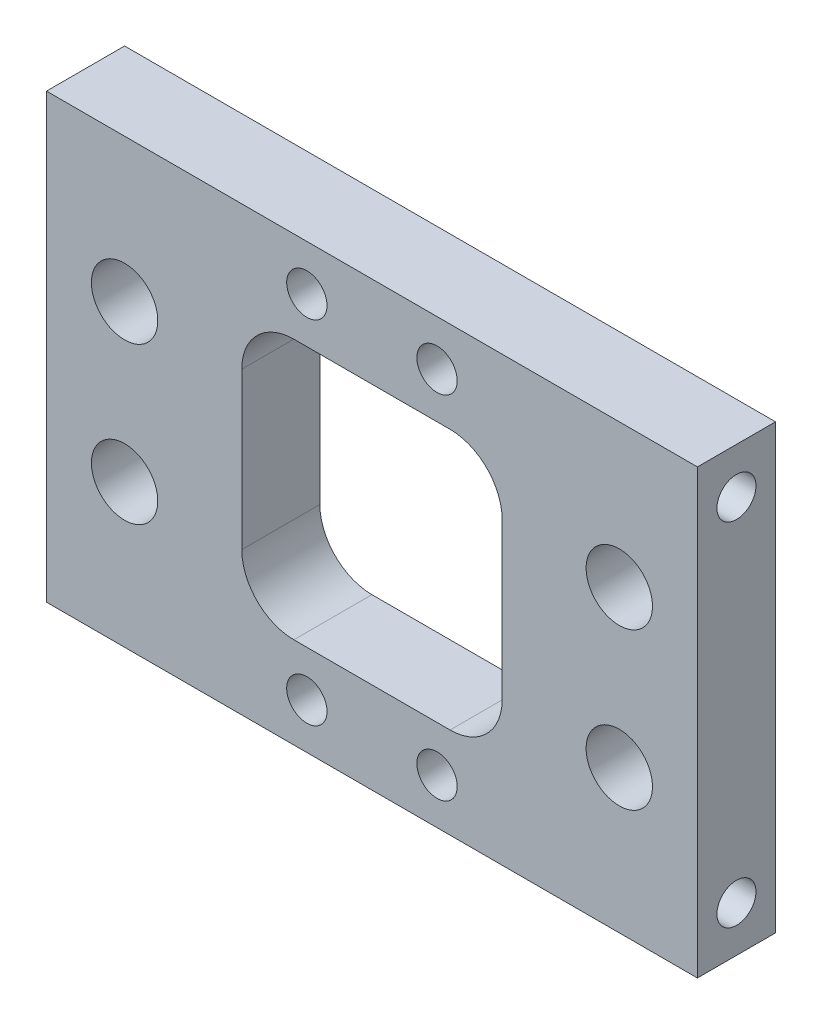
SolidWorks part; units mm, degrees
ref_plane "前视基准面" through (0, 0, 0) normal (0, 0, 1) x (1, 0, 0)
ref_plane "上视基准面" through (0, 0, 0) normal (0, 1, 0) x (1, 0, 0)
ref_plane "右视基准面" through (0, 0, 0) normal (1, 0, 0) x (0, 0, -1)
ref_plane "基准面1" through (0, 0, -3) normal (0, 0, -1) x (-1, 0, 0)
sketch "草图1" plane through (0, 0, -3) normal (0, 0, -1) x (-1, 0, 0)
  line L0 (-25, -17) -> (25, -17)
  line L1 (25, -17) -> (25, 17)
  line L2 (25, 17) -> (-25, 17)
  line L3 (-25, 17) -> (-25, -17)
extrude "凸台-拉伸1" add sketch "草图1" against normal blind 6
sketch "草图2" plane through (0, 0, 3) normal (0, 0, 1) x (1, 0, 0)
  line L0 (10, 10) -> (-10, 10)
  line L1 (-10, 10) -> (-10, -10)
  line L2 (-10, -10) -> (10, -10)
  line L3 (10, -10) -> (10, 10)
extrude "切除-拉伸1" cut sketch "草图2" against normal through all
hole_wizard "Ø5.1 (5.1) 直径孔1" positions "草图4" profile "草图3" hole size "Ø5.1" standard "ANSI Metric" end condition through all
sketch "草图4" plane through (0, 0, -3) normal (0, 0, -1) x (-1, 0, 0)
  point P0 (-19, 6)
  point P1 (19, -6)
  point P2 (-19, -6)
  point P3 (19, 6)
sketch "草图3" plane through (19, 6, -3) normal (1, 0, 0) x (0, 1, 0)
  line L0 (0, 0) -> (0, 6)
  line L1 (0, 6) -> (2.55, 6)
  line L2 (2.55, 6) -> (2.55, 0)
  line L5 (2.55, 0) -> (0, 0)
  line L11 (0, -6.35) -> (0, 107.95) construction
  dimension "通孔孔直径" = 5.1
  dimension "通孔孔深度" = 6
hole_wizard "Ø3.0 (3) 直径孔1" positions "草图6" profile "草图5" hole size "Ø3.0" standard "ANSI Metric"
sketch "草图6" plane through (-25, 0, 0) normal (-1, 0, 0) x (0, 0, 1)
  point P0 (0, -13.5)
  point P1 (0, 13.5)
sketch "草图5" plane through (-25, -13.5, 0) normal (0, 1, 0) x (0, 0, 1)
  line L0 (0, 0) -> (0, 5)
  line L1 (0, 5) -> (1.5, 5)
  line L2 (1.5, 5) -> (1.5, 0)
  line L5 (1.5, 0) -> (0, 0)
  line L10 (0, 5) -> (-1.5, 5) construction
  line L11 (0, -6.35) -> (0, 107.95) construction
  dimension "孔直径" = 3
  dimension "孔深度" = 5
  dimension "导头角度" = 180
hole_wizard "Ø3.0 (3) 直径孔2" positions "草图8" profile "草图7" hole size "Ø3.0" standard "ANSI Metric"
sketch "草图8" plane through (25, 0, 0) normal (1, 0, 0) x (0, 0, -1)
  point P0 (0, -13.5)
  point P1 (0, 13.5)
sketch "草图7" plane through (25, -13.5, 0) normal (0, 1, 0) x (0, 0, -1)
  line L0 (0, 0) -> (0, 5)
  line L1 (0, 5) -> (1.5, 5)
  line L2 (1.5, 5) -> (1.5, 0)
  line L5 (1.5, 0) -> (0, 0)
  line L10 (0, 5) -> (-1.5, 5) construction
  line L11 (0, -6.35) -> (0, 107.95) construction
  dimension "孔直径" = 3
  dimension "孔深度" = 5
  dimension "导头角度" = 180
fillet "圆角1" radius 4 4 edges at (10, -10, 0) (10, 10, 0) (-10, -10, 0) (-10, 10, 0) tangent propagation no
sketch "草图9" plane through (0, 0, 3) normal (0, 0, 1) x (1, 0, 0)
  line L0 (25, -17) -> (-25, -17) construction
  line L1 (25, 17) -> (25, -17) construction
  line L2 (-25, -17) -> (-25, 17) construction
  circle A0 centre (5, -13.5) radius 1.55
  circle A2 centre (-5, -13.5) radius 1.55
  dimension "D1" = 3.1
  dimension "D2" = 3.1
  dimension "D3" = 3.5
  dimension "D5" = 3.5
  dimension "D6" = 20
  dimension "D7" = 20
extrude "切除-拉伸3" cut sketch "草图9" against normal up to next
ref_plane "基准面2" through (0, 0, 0) normal (0, -1, 0) x (-1, 0, 0)
mirror "镜向1" about plane through (0, 0, 0) normal (0, -1, 0) of "切除-拉伸3"
